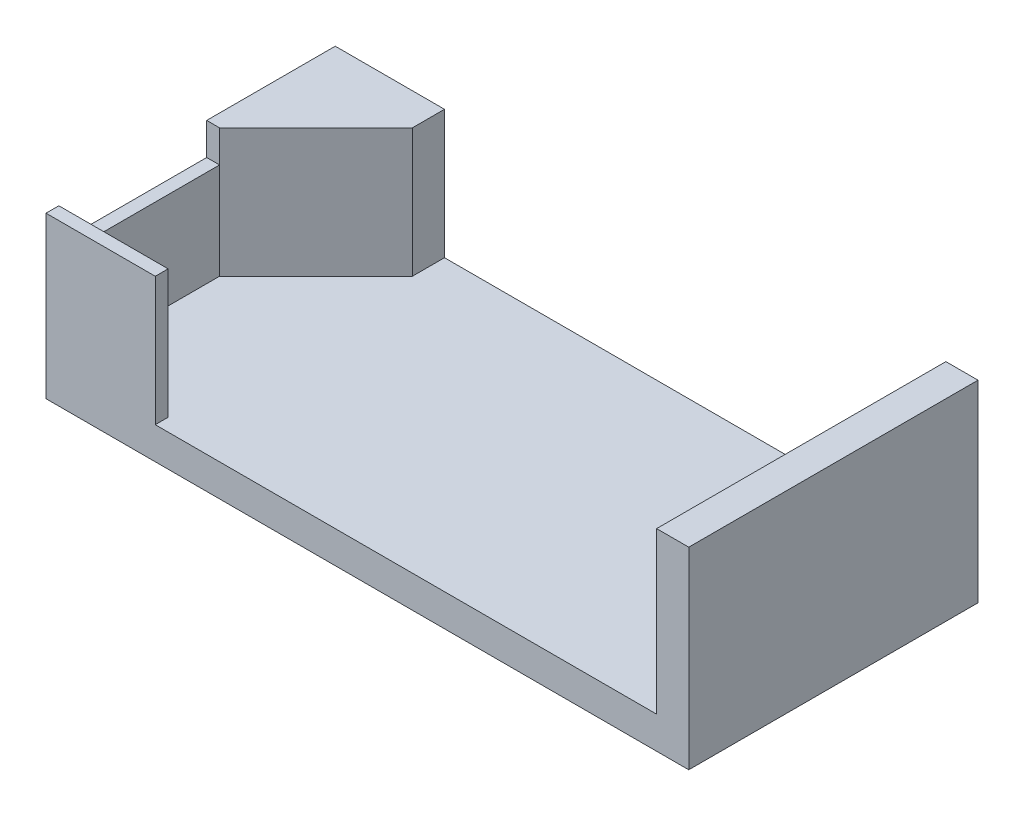
SolidWorks part; units mm, degrees
ref_plane "Front Plane" through (0, 0, 0) normal (0, 0, 1) x (1, 0, 0)
ref_plane "Top Plane" through (0, 0, 0) normal (0, 1, 0) x (1, 0, 0)
ref_plane "Right Plane" through (0, 0, 0) normal (1, 0, 0) x (0, 0, -1)
sketch "Sketch1" plane through (0, 0, 0) normal (0, 1, 0) x (1, 0, 0)
  line L0 (-48, -22.5) -> (-48, 2.5)
  line L1 (-50, -22.5) -> (50, -22.5)
  line L2 (-50, -22.5) -> (-50, 22.5)
  line L3 (-50, 22.5) -> (50, 22.5)
  line L4 (50, -22.5) -> (50, 22.5)
  line L5 (-50, -22.5) -> (50, 22.5) construction
  line L6 (-50, 22.5) -> (50, -22.5) construction
  line L7 (50, -22.5) -> (45, -22.5)
  line L8 (50, -22.5) -> (50, 22.5)
  line L9 (50, 22.5) -> (45, 22.5)
  line L10 (45, -22.5) -> (45, 22.5)
  line L11 (50, -22.5) -> (45, 22.5) construction
  line L12 (50, 22.5) -> (45, -22.5) construction
  line L13 (-48, 2.5) -> (-28, 22.5)
  line L14 (-48, -20.5) -> (-33, -20.5)
  line L15 (-33, -20.5) -> (-33, -22.5)
  line L16 (-33, 17.5) -> (-33, 22.5)
  line L17 (-48, -20.5) -> (-50, -20.5)
  line L18 (-48, 2.5) -> (-50, 2.5)
  point P0 (0, 0)
  point P8 (47.5, 0)
  dimension "D1" = 100
  dimension "D2" = 45
  dimension "D3" = 5
  dimension "D4" = 135
  dimension "D5" = 2
  dimension "D6" = 15
  dimension "10" = 20
  dimension "D7" = 15
  dimension "D8" = 2
extrude "Boss-Extrude1" add sketch "Sketch1" against normal blind 5 contours L18 L13 L16 L3 L2 | L14 L15 L1 L10 L3 L13 L0 | L16 L13 L3 | L10 L1 L4 L3 | L0 L18 L2 L17 | L15 L14 L0 L1 | L0 L17 L2 L1 region at (-49, 0, 21.5) region at (-40.5, 0, 21.5) region at (-49, 0, 9) region at (0.8102, 0, 0.6376) region at (-43.2308, 0, -14.9725) region at (47.5, 0, 0) region at (-31.3333, 0, -20.8333)
extrude "Boss-Extrude2" add sketch "Sketch1<4>" along normal blind 25 contours L10 L1 L4 L3 region at (47.5, 0, 0)
sketch "Sketch1<4>" plane through (0, 0, 0) normal (0, 1, 0) x (1, 0, 0) same geometry as "Sketch1"
extrude "Boss-Extrude3" add sketch "Sketch1<5>" along normal blind 20 contours L15 L14 L0 L1 | L0 L17 L2 L1 region at (-49, 0, 21.5) region at (-40.5, 0, 21.5)
sketch "Sketch1<5>" plane through (0, 0, 0) normal (0, 1, 0) x (1, 0, 0) same geometry as "Sketch1"
extrude "Boss-Extrude4" add sketch "Sketch1<6>" along normal blind 20 contours L18 L13 L16 L3 L2 region at (-43.2308, 0, -14.9725)
sketch "Sketch1<6>" plane through (0, 0, 0) normal (0, 1, 0) x (1, 0, 0) same geometry as "Sketch1"
extrude "Boss-Extrude5" add sketch "Sketch1<8>" along normal blind 15 contours L0 L18 L2 L17 region at (-49, 0, 9)
sketch "Sketch1<8>" plane through (0, 0, 0) normal (0, 1, 0) x (1, 0, 0) same geometry as "Sketch1"
